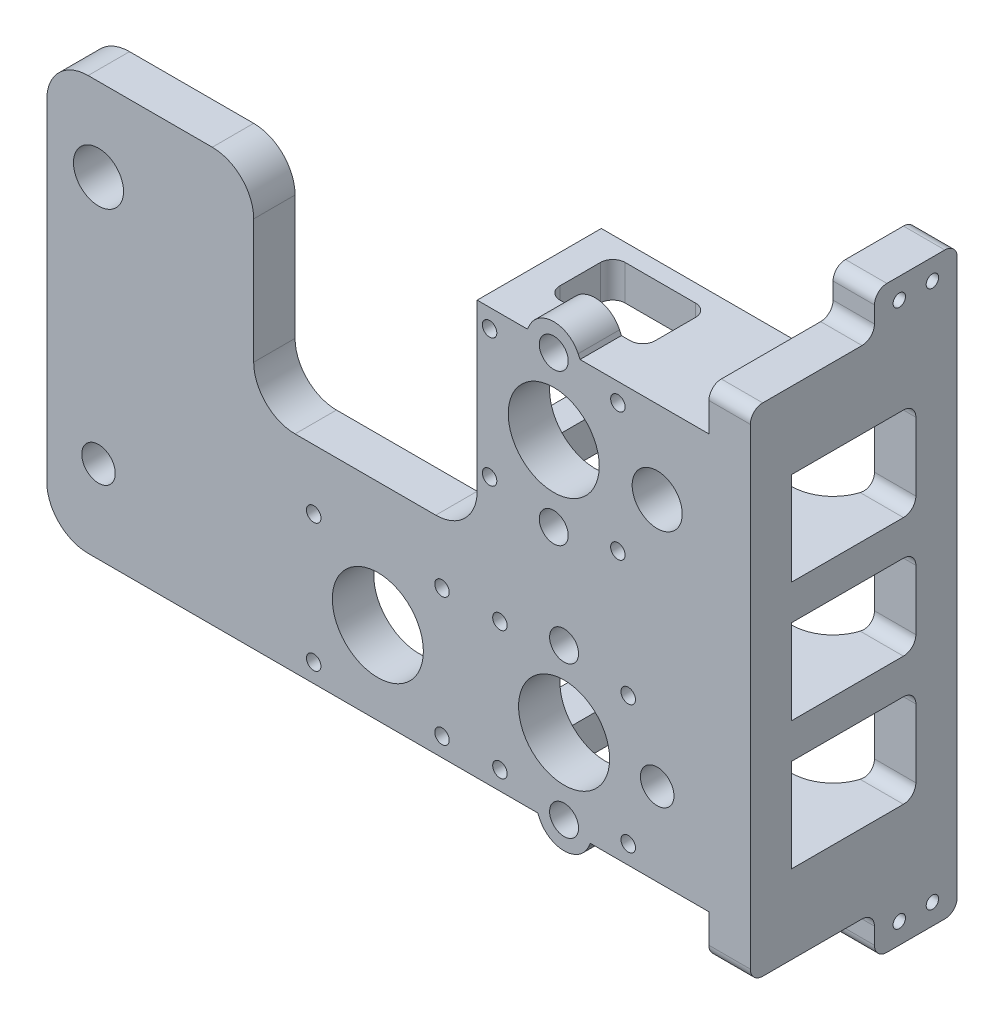
SolidWorks part; units mm, degrees
ref_plane "Front Plane" through (0, 0, 0) normal (0, 0, 1) x (1, 0, 0)
ref_plane "Top Plane" through (0, 0, 0) normal (0, 1, 0) x (1, 0, 0)
ref_plane "Right Plane" through (0, 0, 0) normal (1, 0, 0) x (0, 0, -1)
sketch "Sketch1" plane through (0, 0, 0) normal (0, 0, 1) x (1, 0, 0)
  line L0 (-67.5, 0) -> (67.5, 0) construction
  line L1 (80, 20) -> (48.8534, 20)
  line L2 (80, 20) -> (80, -80)
  line L3 (80, -80) -> (51.3559, -80)
  line L4 (-80, 20) -> (-80, -80)
  line L5 (42.5, -18.25) -> (42.5, 18.25) construction
  line L6 (45, -78.25) -> (45, -41.75) construction
  line L7 (-15.5, -15.5) -> (15.5, -15.5) construction
  line L8 (-15.5, -15.5) -> (-15.5, 15.5) construction
  line L9 (-15.5, 15.5) -> (15.5, 15.5) construction
  line L10 (15.5, -15.5) -> (15.5, 15.5) construction
  line L11 (-15.5, -15.5) -> (15.5, 15.5) construction
  line L12 (-15.5, 15.5) -> (15.5, -15.5) construction
  line L13 (-30, 20) -> (-30, -30)
  line L14 (-67.5, -60) -> (67.5, -60) construction
  line L15 (-67.5, -60) -> (-67.5, 0) construction
  line L16 (-67.5, 0) -> (67.5, 0) construction
  line L17 (67.5, -60) -> (67.5, 0) construction
  line L18 (36.5156, 20.7871) -> (36.1466, 20)
  line L19 (48.3967, 20.9848) -> (48.8534, 20)
  line L20 (-30, -30) -> (24, -30)
  line L21 (24, -30) -> (24, 20)
  line L22 (0, -111.2369) -> (0, 89.7732) construction
  line L23 (-30, 20) -> (-80, 20)
  line L24 (39.109, -80.997) -> (38.6441, -80)
  line L25 (50.891, -80.997) -> (51.3559, -80)
  line L26 (38.6441, -80) -> (-80, -80)
  line L27 (36.1466, 20) -> (24, 20)
  line L28 (24, -30) -> (24, -80) construction
  circle A0 centre (-67.5, 0) radius 6.05
  circle A1 centre (67.5, 0) radius 6.05
  circle A2 centre (67.5, -60) radius 4.05
  circle A3 centre (-67.5, -60) radius 4.05
  circle A4 centre (0, 0) radius 11 construction
  circle A5 centre (15.5, 15.5) radius 1.75 construction
  circle A6 centre (-15.5, 15.5) radius 1.75 construction
  circle A7 centre (-15.5, -15.5) radius 1.75 construction
  circle A8 centre (15.5, -15.5) radius 1.75 construction
  circle A11 centre (-15.5, -44.5) radius 1.75
  circle A12 centre (15.5, -44.5) radius 1.75
  circle A13 centre (0, -60) radius 11
  circle A14 centre (-15.5, -75.5) radius 1.75
  circle A15 centre (15.5, -75.5) radius 1.75
  circle A21 centre (60.5, -44.5) radius 1.75
  circle A22 centre (29.5, -44.5) radius 1.75
  circle A23 centre (45, -60) radius 11
  circle A24 centre (60.5, -75.5) radius 1.75
  circle A25 centre (29.5, -75.5) radius 1.75
  circle A26 centre (42.5, 0) radius 11
  circle A27 centre (58, 15.5) radius 1.75
  circle A28 centre (27, 15.5) radius 1.75
  circle A29 centre (27, -15.5) radius 1.75
  circle A30 centre (58, -15.5) radius 1.75
  circle A31 centre (42.5, -18.25) radius 3.5
  circle A32 centre (45, -41.75) radius 3.5
  circle A33 centre (45, -78.25) radius 3.5
  circle A34 centre (42.5, 18.25) radius 3.5
  arc A35 (48.3967, 20.9848) -> (36.5156, 20.7871) centre (42.5, 18.25) ccw
  arc A36 (39.109, -80.997) -> (50.891, -80.997) centre (45, -78.25) ccw
  point P0 (0, 0)
  point P16 (0, 0)
  point P32 (0, 0)
  point P58 (42.5, 0)
  point P71 (45, -60)
  dimension "D3" = 12.1
  dimension "D4" = 2
  dimension "D5" = 30
  dimension "D6" = 50
  dimension "D7" = 20
  dimension "D8" = 22
  dimension "D10" = 3.5
  dimension "D11" = 20
  dimension "D12" = 2
  dimension "D13" = 36.5
  dimension "D14" = 36.5
  dimension "D16" = 7
  dimension "D18" = 24
  dimension "D19" = 13
  dimension "D20" = 13
  dimension "D24" = 8.1
  dimension "D2" = 100
  dimension "D9" = 31
  dimension "D15" = 80
  dimension "D21" = 310
  dimension "D22" = 310
  dimension "D23" = 160
  dimension "D17" = 2
extrude "Boss-Extrude1" add sketch "Sketch1" along normal blind 10
sketch "Sketch3" plane through (0, 0, 10) normal (0, 0, 1) x (1, 0, 0)
  circle A0 centre (67.5, 0) radius 6
  circle A1 centre (67.5, 0) radius 6.05
  circle A2 centre (67.5, 0) radius 6.05 construction
  circle A3 centre (-67.5, 0) radius 6.05
  circle A4 centre (-67.5, 0) radius 10
  circle A5 centre (67.5, 0) radius 10
  circle A8 centre (-67.5, 0) radius 6.05 construction
  circle A9 centre (-67.5, -60) radius 7
  circle A10 centre (-67.5, -60) radius 4.05
  circle A11 centre (-67.5, -60) radius 4.05 construction
  circle A12 centre (67.5, -60) radius 7
  circle A13 centre (67.5, -60) radius 4.05
  circle A14 centre (67.5, -60) radius 4.05 construction
  circle M11 centre (-67.5, 0) radius 6.05
  circle M12 centre (67.5, 0) radius 6.05
  circle M13 centre (67.5, -60) radius 4.05
  circle M14 centre (-67.5, -60) radius 4.05
  dimension "D1" = 12
  dimension "D2" = 12.1
  dimension "D3" = 20
  dimension "D4" = 12.1
  dimension "D5" = 8.1
  dimension "D6" = 14
  dimension "D7" = 8.1
  dimension "D8" = 14
extrude "Boss-Extrude3" add sketch "Sketch3" against normal blind 20 contours A12 M13 | A5 M12 | A9 M14 | A4 M11 region at (-77.2172, 0, 10) region at (57.7828, 0, 10) region at (-74.302, -60, 10) region at (60.698, -60, 10)
sketch "Sketch4" plane through (80, 0, 0) normal (1, 0, 0) x (0, 0, -1)
  line L0 (-10, -80) -> (-10, 20) construction
  line L1 (40, -90) -> (-10, -90)
  line L2 (40, -90) -> (40, 30)
  line L3 (40, 30) -> (-10, 30)
  line L4 (-10, -90) -> (-10, 30)
  point P5 (-10, -30)
  point P6 (-10, -30)
  dimension "D1" = 120
  dimension "D2" = 50
extrude "Boss-Extrude4" add sketch "Sketch4" along normal blind 10
sketch "Sketch5" plane through (0, 0, 0) normal (0, 0, -1) x (-1, 0, 0)
  line L0 (-80, -80) -> (-80, 20) construction
  line L1 (-24, 20) -> (-80, 20)
  line L2 (-24, 20) -> (-24, 11.5)
  line L3 (-24, 11.5) -> (-80, 11.5)
  line L4 (-80, 20) -> (-80, 11.5)
  line L5 (-24, -11) -> (-24, -19.5)
  line L6 (-24, -11) -> (-80, -11)
  line L7 (-80, -11) -> (-80, -19.5)
  line L8 (-24, -19.5) -> (-80, -19.5)
  line L9 (-24, -40) -> (-24, -48.5)
  line L10 (-24, -40) -> (-80, -40)
  line L11 (-80, -40) -> (-80, -48.5)
  line L12 (-24, -48.5) -> (-80, -48.5)
  line L13 (-24, -71) -> (-24, -79.5)
  line L14 (-24, -79.5) -> (-80, -79.5)
  line L15 (-80, -71) -> (-80, -79.5)
  line L16 (-24, -71) -> (-80, -71)
  dimension "D1" = 8.5
  dimension "D2" = 2
  dimension "D3" = 2
extrude "Boss-Extrude5" add sketch "Sketch5" along normal blind 20
sketch "Sketch6" plane through (0, 0, -40) normal (0, 0, -1) x (-1, 0, 0)
  line L20 (-80, -90) -> (-80, 30)
  line L37 (-80, 30) -> (-90, 30)
  line L38 (-90, 30) -> (-90, -90)
  line L39 (-90, -90) -> (-80, -90)
  line L40 (-80, -90) -> (-80, 30)
  line L57 (-80, 30) -> (-90, 30)
  line L58 (-90, 30) -> (-90, -90)
  line L59 (-90, -90) -> (-80, -90)
  circle A0 centre (-29.5, -75.5) radius 1.75 construction
  circle A1 centre (-60.5, -75.5) radius 1.75 construction
  circle A2 centre (-60.5, -44.5) radius 1.75 construction
  circle A3 centre (-29.5, -44.5) radius 1.75 construction
  circle A4 centre (-58, -15.5) radius 1.75 construction
  circle A5 centre (-27, -15.5) radius 1.75 construction
  circle A6 centre (-27, 15.5) radius 1.75 construction
  circle A7 centre (-58, 15.5) radius 1.75 construction
  circle A8 centre (-29.5, -75.5) radius 1.75
  circle A9 centre (-60.5, -75.5) radius 1.75
  circle A10 centre (-60.5, -44.5) radius 1.75
  circle A11 centre (-29.5, -44.5) radius 1.75
  circle A12 centre (-58, -15.5) radius 1.75
  circle A13 centre (-27, -15.5) radius 1.75
  circle A14 centre (-27, 15.5) radius 1.75
  circle A15 centre (-58, 15.5) radius 1.75
  dimension "D1" = 0
extrude "Cut-Extrude2" cut sketch "Sketch6" against normal up to surface (50 mm away) contours A15 | A14 | A12 | A13 | A10 | A11 | A9 | A8 up to face at (48.5, -78.25, 10)
sketch "Sketch7" plane through (0, 20, 0) normal (0, 1, 0) x (1, 0, 0)
  line L0 (31, 0) -> (54, 0)
  line L1 (31, 0) -> (31, 15.7654)
  line L2 (31, 15.7654) -> (54, 15.7654)
  line L3 (54, 15.7654) -> (54, 0)
  line L4 (24, -10) -> (24, 20) construction
  dimension "D1" = 7
  dimension "D2" = 23
extrude "Cut-Extrude3" cut sketch "Sketch7" against normal up to surface (39.5 mm away) up to face at (48.8333, -19.5, -6.6667)
sketch "Sketch8" plane through (0, -80, 0) normal (0, -1, 0) x (1, 0, 0)
  line L1 (24, -20) -> (24, 0) construction
  line L8 (56.5, 0) -> (33.5, 0)
  line L9 (56.5, -15.7654) -> (56.5, 0)
  line L10 (33.5, -15.7654) -> (56.5, -15.7654)
  line L11 (33.5, 0) -> (33.5, -15.7654)
  dimension "D2" = 23
  dimension "D1" = 9.5
extrude "Cut-Extrude9" cut sketch "Sketch8" against normal up to surface (40 mm away) up to face at (49.6667, -40, -6.6667)
sketch "Sketch10" plane through (90, 0, 0) normal (1, 0, 0) x (0, 0, -1)
  line L0 (40, 30) -> (-10, 30) construction
  line L1 (30, 11.5) -> (0, 11.5)
  line L2 (30, 11.5) -> (30, -11)
  line L3 (30, -11) -> (0, -11)
  line L4 (0, 11.5) -> (0, -11)
  line L5 (30, -48.5) -> (0, -48.5)
  line L6 (30, -48.5) -> (30, -71)
  line L7 (30, -71) -> (0, -71)
  line L8 (0, -48.5) -> (0, -71)
  line L9 (40, -90) -> (40, 30) construction
  line L10 (-10, 30) -> (-10, -90) construction
  line L12 (30, -19.5) -> (0, -19.5)
  line L13 (30, -19.5) -> (30, -40)
  line L14 (30, -40) -> (0, -40)
  line L15 (0, -19.5) -> (0, -40)
  dimension "D1" = 18.5
  dimension "D2" = 22.5
  dimension "D3" = 78.5
  dimension "D4" = 22.5
  dimension "D5" = 10
  dimension "D6" = 10
  dimension "D7" = 8.5
  dimension "D8" = 8.5
extrude "Cut-Extrude10" cut sketch "Sketch10" against normal blind 10
sketch "Sketch11" plane through (0, 30, 0) normal (0, 1, 0) x (1, 0, 0)
  line L0 (80, 40) -> (80, -10) construction
  line L1 (80, 20) -> (90, 20)
  line L2 (80, 20) -> (80, 40)
  line L3 (80, 40) -> (90, 40)
  line L4 (90, 20) -> (90, 40)
  dimension "D1" = 20
extrude "Boss-Extrude6" add sketch "Sketch11" along normal blind 10
sketch "Sketch12" plane through (0, -90, 0) normal (0, -1, 0) x (1, 0, 0)
  line L4 (90, -20) -> (80, -20)
  line L5 (90, -40) -> (90, -20)
  line L6 (80, -40) -> (90, -40)
  line L7 (80, -20) -> (80, -40)
  line L8 (90, -20) -> (80, -20)
  line L9 (90, -40) -> (90, -20)
  line L10 (80, -40) -> (90, -40)
  line L11 (80, -20) -> (80, -40)
  dimension "D1" = 0
extrude "Boss-Extrude7" add sketch "Sketch12" along normal blind 10
fillet "Fillet1" radius 3 30 edges at (56.5, -75.25, 0) (56.5, -44.25, 0) (54, -15.25, 0) (54, 15.75, 0) (56.5, -75.25, -15.7654) (56.5, -44.25, -15.7654) (54, -15.25, -15.7654) (54, 15.75, -15.7654) (33.5, -75.25, 0) (33.5, -44.25, 0) (31, -15.25, 0) (33.5, -75.25, -15.7654) (33.5, -44.25, -15.7654) (31, -15.25, -15.7654) (31, 15.75, -15.7654) (31, 15.75, 0) (85, -11, -30) (85, -40, -30) (85, -71, -30) (85, -48.5, -30) (85, -19.5, -30) (85, 11.5, -30) (85, 40, -20) (85, 40, -40) (85, -100, -20) (85, -100, -40) (85, -90, 10) (85, 30, 10) (85, -90, -20) (85, 30, -20)
fillet "Fillet2" radius 10 9 edges at (-30, 20, 5) (-80, 20, 5) (-80, -80, 5) (24, -30, 5) (-30, -30, 5) (80, 15.75, -20) (80, -15.25, -20) (80, -44.25, -20) (80, -75.25, -20)
sketch "Sketch13" plane through (90, 0, 0) normal (1, 0, 0) x (0, 0, -1)
  line L0 (40, -97) -> (40, 37) construction
  line L1 (23, 40) -> (37, 40) construction
  circle A0 centre (34, 35) radius 1.5
  circle A2 centre (26, 35) radius 1.5
  circle A3 centre (26, -95) radius 1.5
  circle A4 centre (34, -95) radius 1.5
  dimension "D1" = 3
  dimension "D2" = 8
  dimension "D3" = 6
  dimension "D4" = 5
  dimension "D5" = 2
extrude "Cut-Extrude11" cut sketch "Sketch13" against normal blind 10
